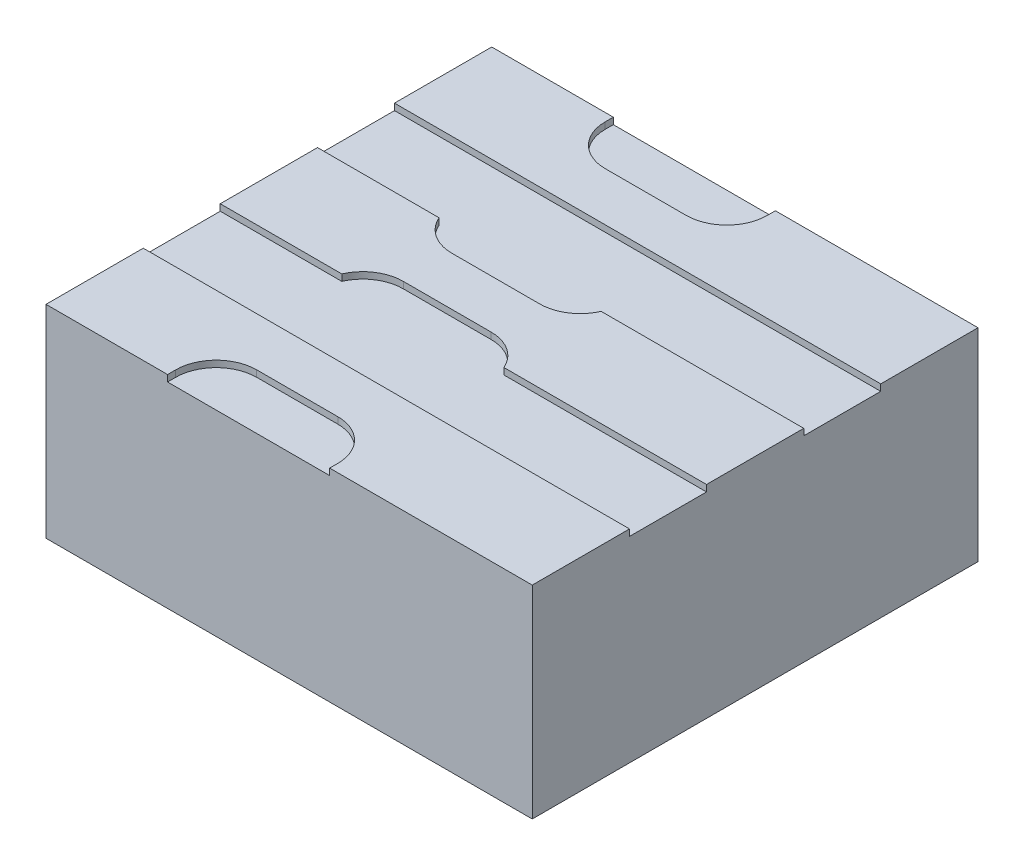
SolidWorks part; units mm, degrees
material "A-Glass Fiber"
ref_plane "Front Plane" through (0, 0, 0) normal (0, 0, 1) x (1, 0, 0)
ref_plane "Top Plane" through (0, 0, 0) normal (0, 1, 0) x (1, 0, 0)
ref_plane "Right Plane" through (0, 0, 0) normal (1, 0, 0) x (0, 0, -1)
sketch "Sketch1" plane through (0, 0, 0) normal (0, 0, 1) x (1, 0, 0)
  line L1 (3, -1.25) -> (-3, -1.25)
  line L2 (3, -1.25) -> (3, 1.25)
  line L3 (3, 1.25) -> (-3, 1.25)
  line L4 (-3, -1.25) -> (-3, 1.25)
  line L5 (3, -1.25) -> (-3, 1.25) construction
  line L6 (3, 1.25) -> (-3, -1.25) construction
  point P0 (0, 0)
  dimension "D1" = 2.5
  dimension "D2" = 6
extrude "Boss-Extrude1" add sketch "Sketch1" along normal mid plane 5.5
sketch "Sketch3" plane through (0, 1.25, 0) normal (0, 1, 0) x (1, 0, 0)
  line L0 (-2, 1.85) -> (2, 1.85) construction
  line L1 (0, 1.85) -> (0, 0) construction
  line L2 (-2, 2.15) -> (2, 2.15)
  line L3 (-2, 1.55) -> (2, 1.55)
  line L4 (-2, 2.15) -> (-2, 1.55)
  line L5 (2, 2.15) -> (2, 1.55)
  line L6 (0, 0) -> (5.6221, 0) construction
  line L7 (-2, -1.85) -> (2, -1.85) construction
  line L8 (2, -2.15) -> (2, -1.55)
  line L9 (-2, -2.15) -> (-2, -1.55)
  line L10 (-2, -1.55) -> (2, -1.55)
  line L11 (-2, -2.15) -> (2, -2.15)
  line L12 (-2, 0) -> (2, 0) construction
  line L13 (-2, -0.3) -> (2, -0.3)
  line L14 (-2, 0.3) -> (2, 0.3)
  line L15 (-2, -0.3) -> (-2, 0.3)
  line L16 (2, -0.3) -> (2, 0.3)
  line L17 (-3, -2.75) -> (-3, 2.75) construction
  dimension "D1" = 1
  dimension "D2" = 1.85
  dimension "D3" = 0.3
  dimension "D4" = 0.3
extrude "Cut-Extrude1" cut sketch "Sketch3" against normal blind 0.08 flip side to cut
sketch "Sketch7" plane through (0, 1.25, 0) normal (0, 1, 0) x (1, 0, 0)
  line L0 (-2, 1.55) -> (2, 1.55) construction
  line L1 (-1.5, 1.55) -> (-3, 1.55)
  line L2 (-1.5, 1.55) -> (-1.5, 2.75)
  line L3 (-1.5, 2.75) -> (-3, 2.75)
  line L4 (-3, 1.55) -> (-3, 2.75)
  line L5 (0, 0) -> (-4.7019, 0) construction
  line L6 (-3, -1.55) -> (-3, -2.75)
  line L7 (-1.5, -2.75) -> (-3, -2.75)
  line L8 (-1.5, -1.55) -> (-1.5, -2.75)
  line L9 (-1.5, -1.55) -> (-3, -1.55)
  line L10 (-2, 1.55) -> (2, 1.55) construction
  line L11 (0.5, 1.55) -> (3, 1.55)
  line L12 (0.5, 1.55) -> (0.5, 2.75)
  line L13 (0.5, 2.75) -> (3, 2.75)
  line L14 (3, 1.55) -> (3, 2.75)
  line L15 (3, -1.55) -> (3, -2.75)
  line L16 (0.5, -2.75) -> (3, -2.75)
  line L17 (0.5, -1.55) -> (0.5, -2.75)
  line L18 (0.5, -1.55) -> (3, -1.55)
  line L19 (-3, 2.75) -> (-3, -2.75) construction
  line L20 (-1.5, -0.6) -> (-3, -0.6)
  line L21 (-1.5, -0.6) -> (-1.5, 0.6)
  line L22 (-1.5, 0.6) -> (-3, 0.6)
  line L23 (-3, -0.6) -> (-3, 0.6)
  line L24 (-1.5, -0.6) -> (-3, 0.6) construction
  line L25 (-1.5, 0.6) -> (-3, -0.6) construction
  line L26 (0.5, -0.6) -> (0.5, 0.6)
  line L27 (0.5, 0.6) -> (3, 0.6)
  line L28 (0.5, -0.6) -> (3, -0.6)
  line L29 (3, -0.6) -> (3, 0.6)
  point P25 (-2.25, 0)
  dimension "D1" = 1.5
  dimension "D2" = 2.5
extrude "Boss-Extrude3" add sketch "Sketch7" against normal blind 0.2
fillet "Fillet2" radius 0.5 8 edges at (0.5, 1.21, -2.15) (-1.5, 1.21, -2.15) (-1.5, 1.21, 2.15) (0.5, 1.21, 2.15) (0.5, 1.21, -0.3) (0.5, 1.21, 0.3) (-1.5, 1.21, 0.3) (-1.5, 1.21, -0.3) tangent propagation no
